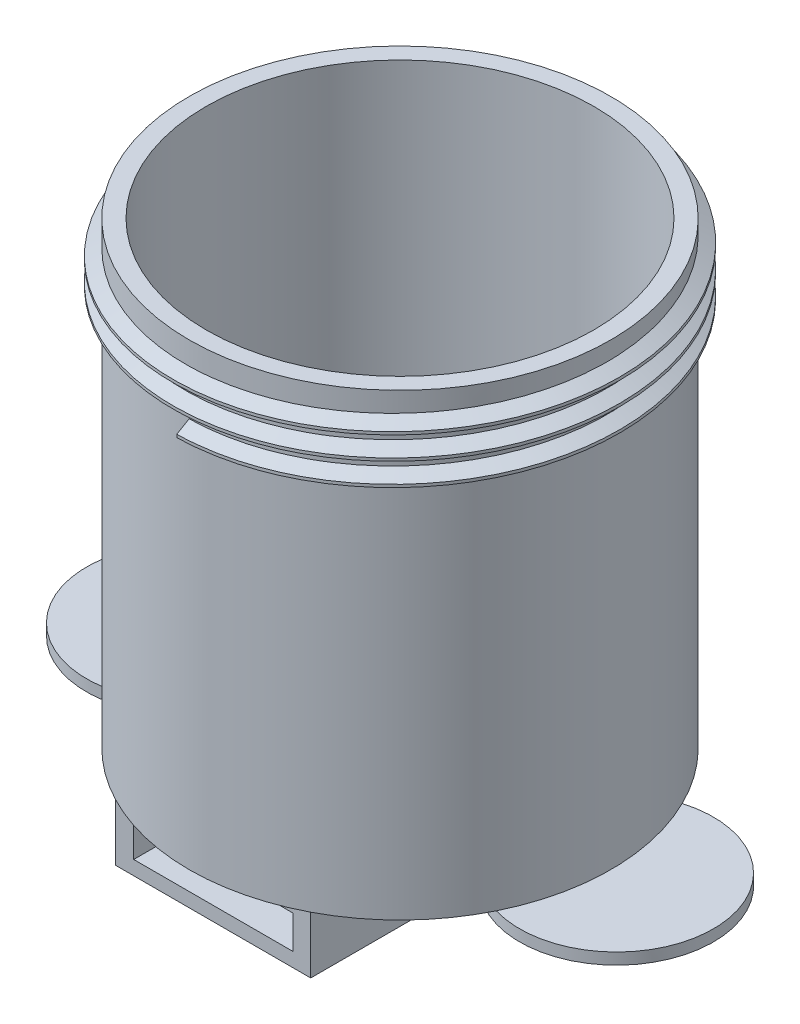
SolidWorks part; units mm, degrees
ref_plane "Ebene vorne" through (0, 0, 0) normal (0, 0, 1) x (1, 0, 0)
ref_plane "Ebene oben" through (0, 0, 0) normal (0, 1, 0) x (1, 0, 0)
ref_plane "Ebene rechts" through (0, 0, 0) normal (1, 0, 0) x (0, 0, -1)
sketch "Skizze1" plane through (0, 0, 0) normal (0, 0, 1) x (1, 0, 0)
  line L0 (0, 0) -> (0, -87.7092) construction
  line L1 (-5.272, -87.7092) -> (-37, -87.7092)
  line L2 (-37, -87.7092) -> (-37, -7.2092)
  line L3 (-37, -7.2092) -> (-34, -7.2092)
  line L4 (-34, -7.2092) -> (-34, -84.7092)
  line L5 (-34, -84.7092) -> (-5, -84.7092)
  line L6 (0, -83.7092) -> (-5.3925, -83.7092) construction
  line L7 (0, -83.7092) -> (0, -85.7566)
  arc A0 (0, -83.7092) -> (-5, -84.7092) centre (-1.243, -90.494) ccw
  arc A1 (0, -85.7566) -> (-5.272, -87.7092) centre (-1.243, -90.494) ccw
  arc A2 (-0.3604, -85.6765) -> (-3.9107, -86.3865) centre (-1.243, -90.494) ccw construction
  dimension "D1" = 74
  dimension "D2" = 3
  dimension "D3" = 3
  dimension "D4" = 5
  dimension "D5" = 4
  dimension "D7" = 80.5
  dimension "D6" = 2
revolve "Rotation1" add sketch "Skizze1" angle 360 about L0
thread "Gewinde2" pitch 4 method extrude profile "Gewindeprofil3" start angle 0, offset 1, length 11, pitch 4, diameter 74
ref_plane "Ebene3" through (-37, -8.2092, 0) normal (0, 0, 1) x (-1, 0, 0)
sketch "Gewindeprofil3" plane through (-37, -8.2092, 0) normal (0, 0, 1) x (-1, 0, 0)
  line L0 (0, 0) -> (0, 4) construction
  line L1 (0, 0) -> (2.1651, 1.25)
  line L2 (2.1651, 1.25) -> (2.1651, 1.75)
  line L3 (2.1651, 1.75) -> (0, 3)
  line L4 (2.1651, 1.5) -> (0, 1.5) construction
  line L11 (0, 0) -> (0, 3)
  point P2 (0, 0)
  dimension "Pitch" = 4
  dimension "Profile_Angle" = 60
  dimension "Profile_Land" = 0.5
  dimension "Profile_Height" = 2.1651
sketch "Skizze23" plane through (0, -87.7092, 0) normal (0, -1, 0) x (1, 0, 0)
  circle A0 centre (-38, 0) radius 17
  circle A1 centre (38, 0) radius 17
  dimension "D1" = 34
  dimension "D2" = 34
  dimension "D3" = 38
  dimension "D4" = 38
extrude "Aufsatz-Linear austragen1" add sketch "Skizze23" along normal blind 2
sketch "Skizze24" plane through (0, -89.7092, 0) normal (0, -1, 0) x (1, 0, 0)
  circle A0 centre (-38.5701, 0) radius 6.5
  circle A1 centre (38.3425, 0) radius 6.5
  dimension "D1" = 13
  dimension "D2" = 13
extrude "Aufsatz-Linear austragen2" add sketch "Skizze24" along normal blind 5
sketch "Skizze28" plane through (0, -87.7092, 0) normal (0, -1, 0) x (1, 0, 0)
  line L1 (-17.1305, 32.7955) -> (17.1305, 32.7955)
  line L2 (-17.1305, 32.7955) -> (-17.1305, -32.7955)
  line L3 (-17.1305, -32.7955) -> (17.1305, -32.7955)
  line L4 (17.1305, 32.7955) -> (17.1305, -32.7955)
  line L5 (-17.1305, 32.7955) -> (17.1305, -32.7955) construction
  line L6 (-17.1305, -32.7955) -> (17.1305, 32.7955) construction
  circle A0 centre (0, 0) radius 37 construction
  point P0 (0, 0)
  dimension "D1" = 65.591
extrude "Aufsatz-Linear austragen3" add sketch "Skizze28" along normal blind 10
sketch "Skizze29" plane through (0, 0, 32.7955) normal (0, 0, 1) x (1, 0, 0)
  line L1 (-13.9309, -89.3985) -> (14.052, -89.3985)
  line L2 (-13.9309, -89.3985) -> (-13.9309, -95.2287)
  line L3 (-13.9309, -95.2287) -> (14.052, -95.2287)
  line L4 (14.052, -89.3985) -> (14.052, -95.2287)
  line L5 (-13.9309, -89.3985) -> (14.052, -95.2287) construction
  line L6 (-13.9309, -95.2287) -> (14.052, -89.3985) construction
  point P0 (0.0606, -92.3136)
extrude "Schnitt-Linear austragen1" cut sketch "Skizze29" against normal blind 10
mirror "Spiegeln1" about plane through (0, 0, 0) normal (0, 0, 1) of "Schnitt-Linear austragen1"
